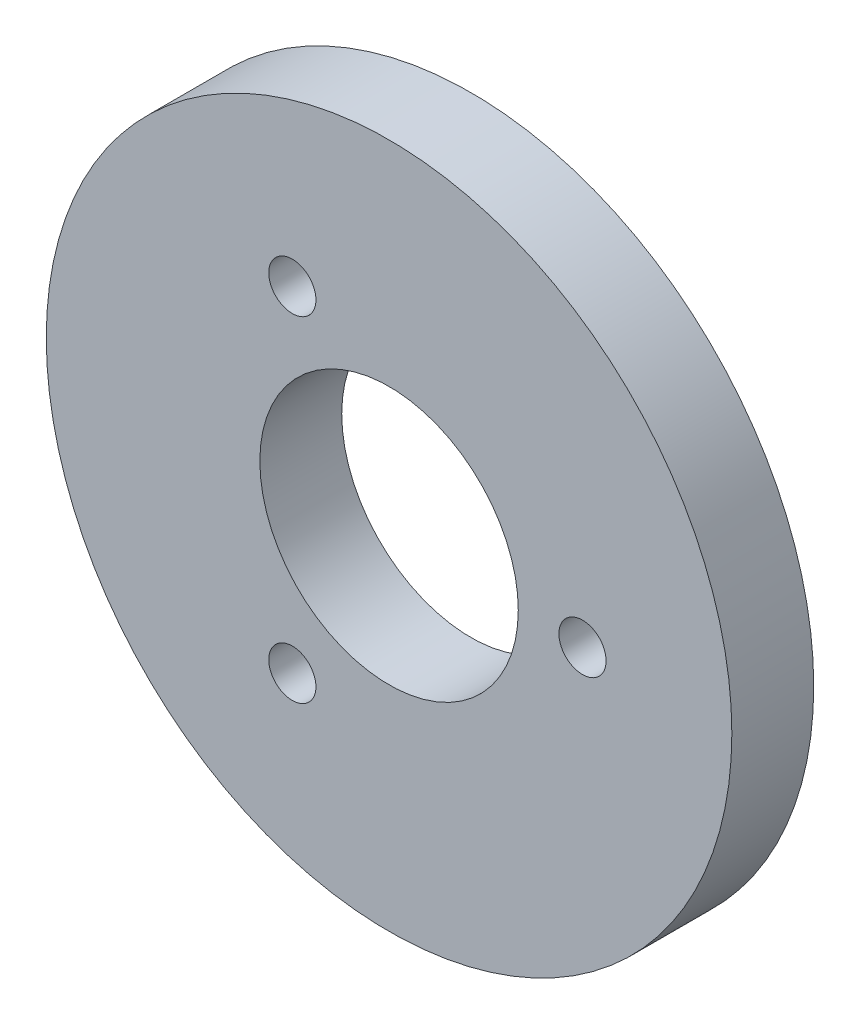
SolidWorks part; units mm, degrees
ref_plane "Front Plane" through (0, 0, 0) normal (0, 0, 1) x (1, 0, 0)
ref_plane "Top Plane" through (0, 0, 0) normal (0, 1, 0) x (1, 0, 0)
ref_plane "Right Plane" through (0, 0, 0) normal (1, 0, 0) x (0, 0, -1)
sketch "Sketch1" plane through (0, 0, 0) normal (0, 0, 1) x (1, 0, 0)
  circle A1 centre (123.7391, 1.2823) radius 10.0203 construction
  circle A2 centre (123.7391, 1.2823) radius 26.5811
  circle A3 centre (123.7391, 1.2823) radius 26.5811
  circle A4 centre (138.7391, 1.2823) radius 1.8288 construction
  circle A5 centre (116.2391, -11.7081) radius 1.8288 construction
  circle A6 centre (116.2391, 14.2727) radius 1.8288 construction
  circle A7 centre (123.7391, 1.2823) radius 10.0203
  circle A8 centre (138.7391, 1.2823) radius 1.8288
  circle A9 centre (116.2391, -11.7081) radius 1.8288
  circle A10 centre (116.2391, 14.2727) radius 1.8288
  dimension "D1" = 6.35
extrude "Boss-Extrude1" add sketch "Sketch1" along normal blind 6.35
